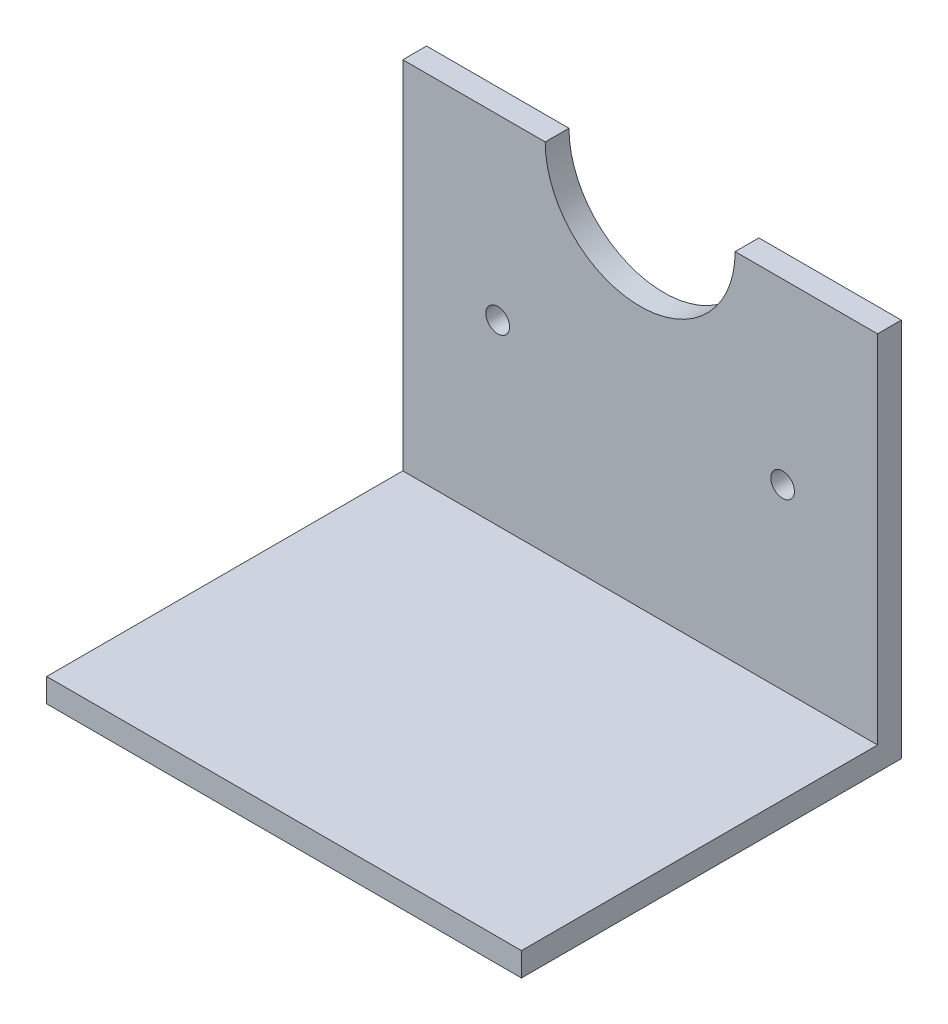
SolidWorks part; units mm, degrees
ref_plane "Front Plane" through (0, 0, 0) normal (0, 0, 1) x (1, 0, 0)
ref_plane "Top Plane" through (0, 0, 0) normal (0, 1, 0) x (1, 0, 0)
ref_plane "Right Plane" through (0, 0, 0) normal (1, 0, 0) x (0, 0, -1)
sketch "Sketch1" plane through (0, 0, 0) normal (1, 0, 0) x (0, 0, -1)
  line L1 (-3.175, 0) -> (-50.8, 0)
  line L2 (0, 0) -> (0, -3.175)
  line L3 (0, -3.175) -> (-50.8, -3.175)
  line L4 (-50.8, 0) -> (-50.8, -3.175)
  line L6 (0, 0) -> (0, 47.625)
  line L7 (0, 47.625) -> (-3.175, 47.625)
  line L8 (-3.175, 0) -> (-3.175, 47.625)
  dimension "D1" = 3.175
  dimension "D2" = 50.8
  dimension "D3" = 50.8
  dimension "D4" = 3.175
extrude "Boss-Extrude1" add sketch "Sketch1" along normal blind 63.5
sketch "Sketch2" plane through (0, 0, 3.175) normal (0, 0, 1) x (1, 0, 0)
  line L0 (12.7, 23.8125) -> (50.8, 23.8125) construction
  line L3 (31.75, 23.8125) -> (31.75, 47.625) construction
  line L4 (63.5, 47.625) -> (0, 47.625) construction
  circle A0 centre (31.75, 47.625) radius 12.7
  circle A1 centre (12.7, 23.8125) radius 1.5875
  circle A2 centre (50.8, 23.8125) radius 1.5875
  point P2 (0, 0)
  point P15 (0, 0)
  dimension "D1" = 25.4
  dimension "D2" = 3.175
  dimension "D3" = 38.1
extrude "Cut-Extrude1" cut sketch "Sketch2" against normal up to surface (3.175 mm away) up to face at (31.75, 22.225, 0)
